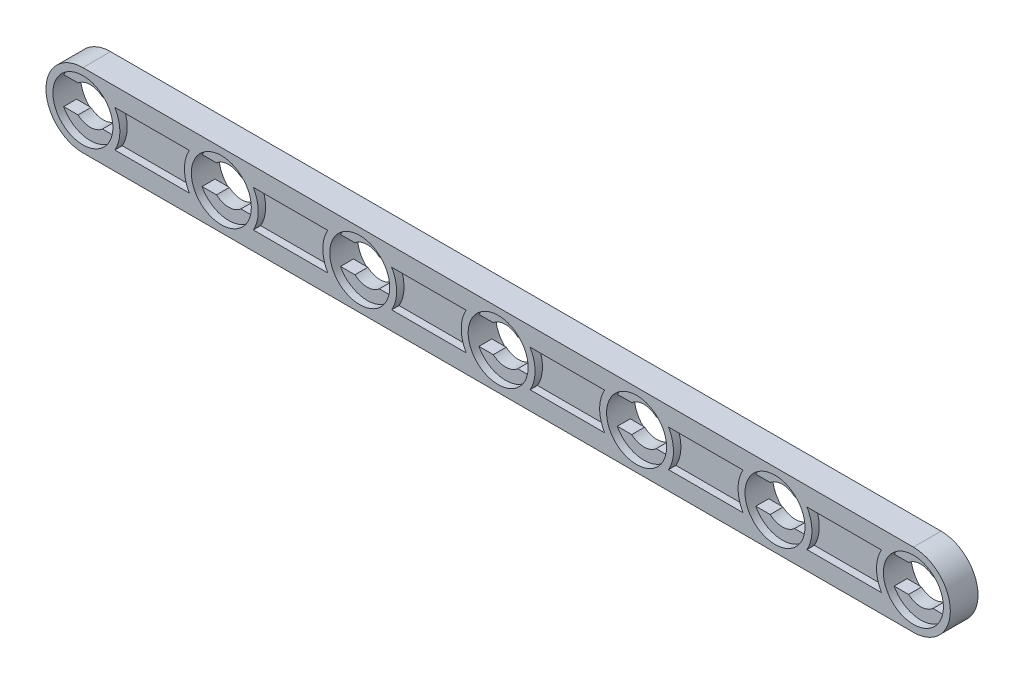
SolidWorks part; units mm, degrees
ref_plane "前视基准面" through (0, 0, 0) normal (0, 0, 1) x (1, 0, 0)
ref_plane "上视基准面" through (0, 0, 0) normal (0, 1, 0) x (1, 0, 0)
ref_plane "右视基准面" through (0, 0, 0) normal (1, 0, 0) x (0, 0, -1)
sketch "草图1" plane through (0, 0, 0) normal (0, 0, 1) x (1, 0, 0)
  line L1 (0, 4) -> (90, 4)
  line L3 (0, -4) -> (90, -4)
  arc A0 (0, 4) -> (0, -4) centre (0, 0) ccw
  arc A2 (90, -4) -> (90, 4) centre (90, 0) ccw
extrude "凸台-拉伸1" add sketch "草图1" against normal blind 3
sketch "草图2" plane through (0, 0, 0) normal (0, 0, 1) x (1, 0, 0)
  line L0 (1.3229, -1.5) -> (2.8831, -1.5)
  line L1 (-2.8831, -1.5) -> (-1.3229, -1.5)
  line L2 (1.3229, 1.5) -> (2.8831, 1.5)
  line L3 (-2.8831, 1.5) -> (-1.3229, 1.5)
  arc A0 (1.3229, 1.5) -> (-1.3229, 1.5) centre (0, 0) ccw
  arc A1 (-2.8831, 1.5) -> (-2.8831, -1.5) centre (0, 0) ccw
  arc A3 (2.8831, -1.5) -> (2.8831, 1.5) centre (0, 0) ccw
  arc A4 (-1.3229, -1.5) -> (1.3229, -1.5) centre (0, 0) ccw
extrude "切除-拉伸1" cut sketch "草图2" against normal up to next
sketch "草图3" plane through (0, 0, 0) normal (0, 0, 1) x (1, 0, 0)
  circle A1 centre (0, 0) radius 3.25
extrude "切除-拉伸2" cut sketch "草图3" against normal blind 0.8
extrude "切除-拉伸3" cut sketch "草图3<2>" along normal blind 0.8 from offset 3 offset against normal yes
sketch "草图3<2>" plane through (0, 0, 0) normal (0, 0, 1) x (1, 0, 0) same geometry as "草图3"
sketch "草图4" plane through (0, 0, 0) normal (0, 0, 1) x (1, 0, 0)
  line L1 (3.4641, 2) -> (11.5359, 2)
  line L3 (3.4641, -2) -> (11.5359, -2)
  arc A0 (11.5359, 2) -> (11.5359, -2) centre (15, 0) ccw
  arc A2 (3.4641, -2) -> (3.4641, 2) centre (0, 0) ccw
extrude "切除-拉伸4" cut sketch "草图4" against normal blind 0.8
sketch "草图5" plane through (0, 0, -3) normal (0, 0, -1) x (-1, 0, 0)
  line L1 (-4, -2) -> (-11, -2)
  line L2 (-4, -2) -> (-4, 2)
  line L3 (-4, 2) -> (-11, 2)
  line L4 (-11, -2) -> (-11, 2)
extrude "切除-拉伸6" cut sketch "草图5" against normal blind 0.8
ref_plane "基准面1" through (7.5, 0, 0) normal (1, 0, 0) x (0, 0, -1)
mirror "镜向1" about plane through (7.5, 0, 0) normal (1, 0, 0) of "切除-拉伸3", "切除-拉伸2", "切除-拉伸1"
ref_plane "基准面2" through (22.5, 0, 0) normal (1, 0, 0) x (0, 0, -1)
ref_plane "基准面3" through (15, 0, 0) normal (1, 0, 0) x (0, 0, -1)
mirror "镜向3" about plane through (15, 0, 0) normal (1, 0, 0) of "切除-拉伸6", "切除-拉伸4"
mirror "镜向4" about plane through (22.5, 0, 0) normal (1, 0, 0) of "切除-拉伸4", "切除-拉伸6"
ref_plane "基准面6" through (37.5, 0, 0) normal (1, 0, 0) x (0, 0, -1)
mirror "镜向7" about plane through (15, 0, 0) normal (1, 0, 0) of "切除-拉伸3", "切除-拉伸2", "切除-拉伸1"
mirror "镜向8" about plane through (37.5, 0, 0) normal (1, 0, 0) of "镜向7", "镜向3", "镜向1", "切除-拉伸6", "切除-拉伸4", "切除-拉伸3", "切除-拉伸2", "切除-拉伸1"
ref_plane "基准面7" through (45, 0, 0) normal (1, 0, 0) x (0, 0, -1)
mirror "镜向9" about plane through (45, 0, 0) normal (1, 0, 0) of "切除-拉伸6", "切除-拉伸4", "切除-拉伸3", "切除-拉伸2", "切除-拉伸1"
